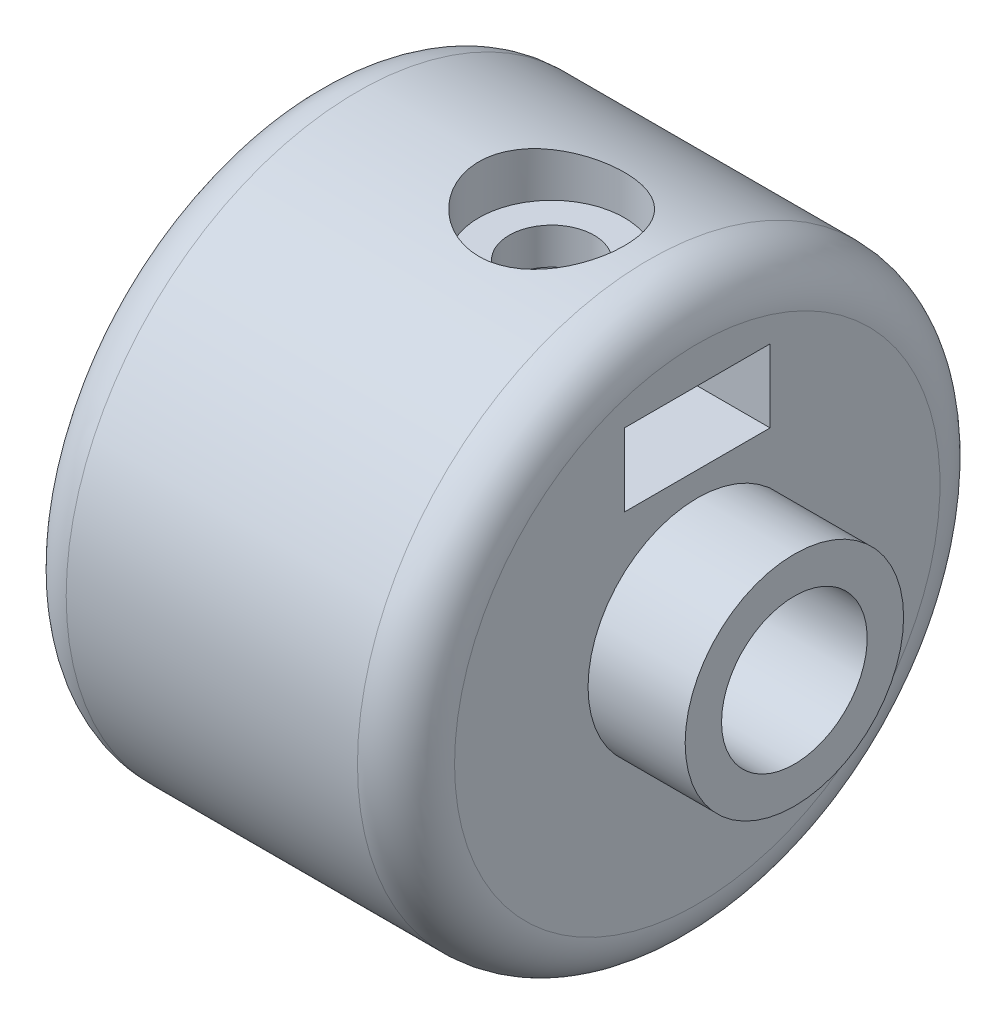
SolidWorks part; units mm, degrees
ref_plane "前视基准面" through (0, 0, 0) normal (0, 0, 1) x (1, 0, 0)
ref_plane "上视基准面" through (0, 0, 0) normal (0, 1, 0) x (1, 0, 0)
ref_plane "右视基准面" through (0, 0, 0) normal (1, 0, 0) x (0, 0, -1)
sketch "草图1" plane through (0, 0, 0) normal (0, 0, 1) x (1, 0, 0)
  line L0 (-12.0159, 0) -> (12.7091, 0) construction
  line L1 (0, 0) -> (0, 10.5504) construction
  line L2 (-15, 3) -> (0, 3)
  line L3 (-15, 3) -> (-15, 0)
  line L4 (-20, 0) -> (-15, 0)
  line L5 (0, 4.5) -> (-4, 4.5)
  line L6 (-4, 4.5) -> (-4, 12)
  line L7 (-4, 12) -> (-20, 12)
  line L8 (0, 4.5) -> (0, 3)
  line L9 (-20, 12) -> (-20, 0)
  dimension "D1" = 3
  dimension "D2" = 12
  dimension "D3" = 4.5
  dimension "D4" = 4
  dimension "D5" = 15
  dimension "D6" = 5
revolve "旋转1" add sketch "草图1" angle 360 about L0
sketch "草图2" plane through (0, 0, 0) normal (0, 1, 0) x (1, 0, 0)
  line L0 (0, 0) -> (-23.5637, 0) construction
  circle A0 centre (-10, 0) radius 1.75
  circle A1 centre (-10, 0) radius 3
  dimension "D1" = 3.5
  dimension "D2" = 6
  dimension "D3" = 10
extrude "切除-拉伸5" cut sketch "草图2" along normal through all contours A0
extrude "切除-拉伸6" cut sketch "草图2<4>" against normal blind 2 from offset 12 contours A1
sketch "草图2<4>" plane through (0, 0, 0) normal (0, 1, 0) x (1, 0, 0) same geometry as "草图2"
sketch "草图4" plane through (0, 0, 0) normal (1, 0, 0) x (0, 0, -1)
  line L0 (0, 0) -> (0, 14.6396) construction
  line L2 (-3, 8.5) -> (3, 8.5)
  line L3 (-3, 8.5) -> (-3, 5.5)
  line L4 (-3, 5.5) -> (3, 5.5)
  line L5 (3, 8.5) -> (3, 5.5)
  line L6 (-3, 8.5) -> (3, 5.5) construction
  line L7 (-3, 5.5) -> (3, 8.5) construction
  point P1 (0, 7)
  dimension "D1" = 3
  dimension "D2" = 6
  dimension "D3" = 7
extrude "切除-拉伸7" cut sketch "草图4" against normal blind 15
fillet "圆角1" radius 2 2 edges at (-20, 0, 12) (-4, 0, 12)
